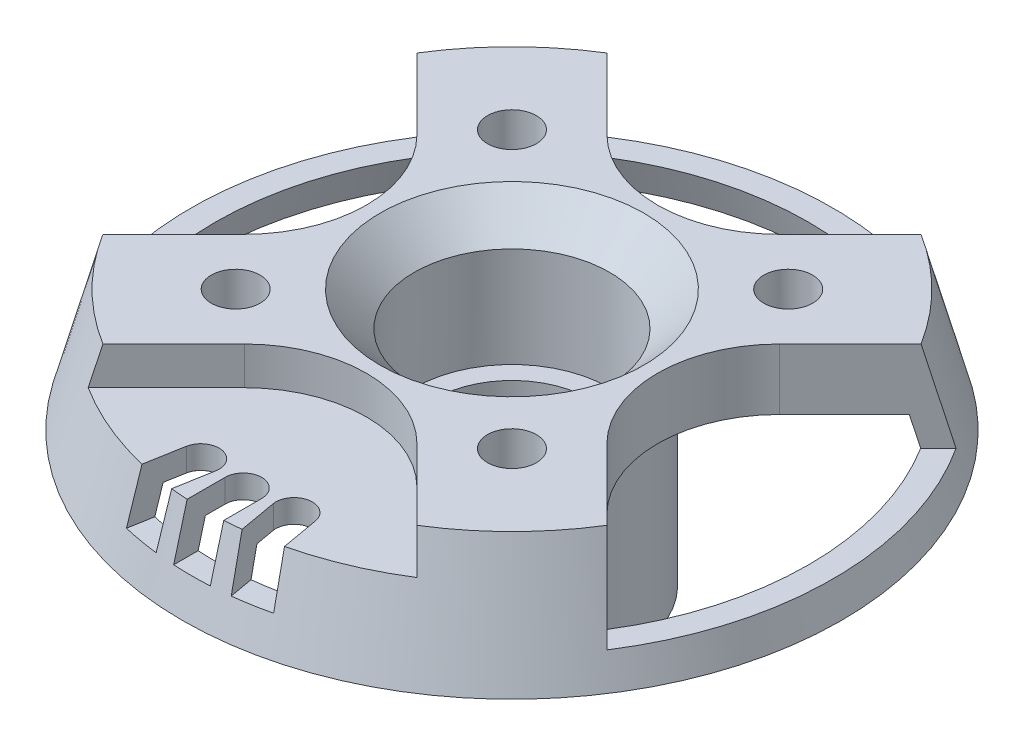
SolidWorks part; units mm, degrees
ref_plane "Front Plane" through (0, 0, 0) normal (0, 0, 1) x (1, 0, 0)
ref_plane "Top Plane" through (0, 0, 0) normal (0, 1, 0) x (1, 0, 0)
ref_plane "Right Plane" through (0, 0, 0) normal (1, 0, 0) x (0, 0, -1)
sketch "Sketch1" plane through (0, 0, 0) normal (0, 1, 0) x (1, 0, 0)
  circle A0 centre (0, 0) radius 13.5
  dimension "D1" = 27
extrude "Base size" add sketch "Sketch1" along normal blind 5
sketch "Sketch2" plane through (0, 5, 0) normal (0, 1, 0) x (1, 0, 0)
  line L0 (-9.5459, -9.5459) -> (9.5459, 9.5459) construction
  line L1 (-13.5, 0) -> (13.5, 0) construction
  line L2 (-9.5459, 9.5459) -> (9.5459, -9.5459) construction
  line L3 (0, 13.5) -> (0, -13.5) construction
  circle A0 centre (0, 0) radius 13.5 construction
  circle A1 centre (5.6569, 5.6569) radius 1
  circle A2 centre (-5.6569, -5.6569) radius 1
  circle A3 centre (5.6569, -5.6569) radius 1
  circle A4 centre (-5.6569, 5.6569) radius 1
  dimension "D2" = 2
  dimension "D1" = 45
  dimension "D3" = 16
extrude "Mounting holes" cut sketch "Sketch2" against normal up to next
sketch "Sketch3" plane through (0, 0, 0) normal (0, -1, 0) x (1, 0, 0)
  circle A0 centre (0, 0) radius 12.5
  circle A1 centre (0, 0) radius 13.5 construction
  dimension "D1" = 1
extrude "Rotor pocket" cut sketch "Sketch3" against normal blind 2.5 draft 15
chamfer "Outside chamfer" distance 5 angle 15 1 edges at (0, 5, 13.5) first distance on face at (0, 5, 13.5)
sketch "Sketch4" plane through (0, 5, 0) normal (0, 1, 0) x (1, 0, 0)
  line L0 (-8.5986, 8.5986) -> (8.5986, -8.5986) construction
  line L1 (-5.6569, 5.6569) -> (5.6569, 5.6569) construction
  line L2 (0, 12.1603) -> (0, -12.1603) construction
  line L3 (-12.1603, 0) -> (12.1603, 0) construction
  line L4 (-8.5986, -8.5986) -> (8.5986, 8.5986) construction
  line L5 (-10.5431, 6.6541) -> (6.6541, -10.5431)
  line L6 (-6.6541, -10.5431) -> (10.5431, 6.6541)
  line L7 (-6.6541, 10.5431) -> (10.5431, -6.6541)
  line L8 (-10.5431, -6.6541) -> (6.6541, 10.5431)
  line L9 (-10.5431, 6.6541) -> (-11.2903, 7.4012)
  line L10 (-6.6541, 10.5431) -> (-7.4012, 11.2903)
  line L11 (6.6541, 10.5431) -> (7.4012, 11.2903)
  line L12 (10.5431, 6.6541) -> (11.2903, 7.4012)
  line L13 (10.5431, -6.6541) -> (11.2903, -7.4012)
  line L14 (6.6541, -10.5431) -> (7.4012, -11.2903)
  line L15 (-6.6541, -10.5431) -> (-7.4012, -11.2903)
  line L16 (-10.5431, -6.6541) -> (-11.2903, -7.4012)
  circle A0 centre (0, 0) radius 12.1603 construction
  circle A1 centre (0, 0) radius 13.5
  circle A2 centre (0, 0) radius 13.5 construction
  circle M9 centre (0, 0) radius 12.1603
  dimension "D1" = 2.75
  dimension "D2" = 2.75
extrude "Bottom pockets top" cut sketch "Sketch4" against normal blind 1.55 contours L8 L5 M9 | L9 A1 L16 L8 L5 M9 | L7 L8 M9 | L11 A1 L10 L7 L8 M9 | L6 L7 M9 | L13 A1 L12 L6 L7 M9 | L15 A1 L14 L5 L6 M9 | L6 L5 M9 region at (-12.1626, 5, 0) region at (-8.9824, 5, 0) region at (0, 5, -8.9824) region at (0, 5, -12.1626) region at (0, 5, 8.9824) region at (0, 5, 12.1626) region at (8.9824, 5, 0) region at (12.1626, 5, 0)
sketch "Sketch5" plane through (0, 3.45, 0) normal (0, 1, 0) x (1, 0, 0)
  line L0 (-11.2903, 7.4012) -> (7.4012, -11.2903)
  line L1 (-10.3204, 6.4313) -> (-3.8891, 0) construction
  line L2 (7.4012, 11.2903) -> (-11.2903, -7.4012)
  line L3 (-10.3204, -6.4313) -> (-3.8891, 0) construction
  line L4 (-7.4012, 11.2903) -> (11.2903, -7.4012)
  line L5 (-6.4313, 10.3204) -> (0, 3.8891) construction
  line L6 (-7.4012, -11.2903) -> (11.2903, 7.4012)
  line L7 (3.8891, 0) -> (10.6216, 6.7325) construction
  circle A0 centre (0, 0) radius 13.5
  circle A1 centre (0, 0) radius 13.5 construction
  line M5 (-10.6216, -6.7325) -> (-3.8891, 0)
  line M6 (-3.8891, 0) -> (-10.6216, 6.7325)
  arc M7 (-10.6216, 6.7325) -> (-10.6216, -6.7325) centre (0, 0) ccw
extrude "Bottom pockets bottom" cut sketch "Sketch5" against normal offset from surface (2.15 mm away) 1.3 contours M7 M5 M6 | L0 A0 L2 M7 | L2 A0 L4 | L4 A0 L6 region at (-11.0626, 3.45, -6.9602) region at (-9.2333, 3.45, 0) region at (0, 3.45, -9.7912) region at (9.7912, 3.45, 0) up to face at (0, 0, -12.5)
fillet "Bottom pockets fillet" radius 5 4 edges at (0, 4.225, 3.8891) (3.8891, 3.75, 0) (0, 3.75, -3.8891) (-3.8891, 3.75, 0)
sketch "Sketch6" plane through (0, 5, 0) normal (0, 1, 0) x (1, 0, 0)
  circle A0 centre (0, 0) radius 4
  dimension "D1" = 8
extrude "Cut-Extrude5" cut sketch "Sketch6" against normal up to next
chamfer "Chamfer2" distance 1.4 angle 45 1 edges at (0, 5, 4)
sketch "Sketch7" plane through (0, 2.5, 0) normal (0, -1, 0) x (1, 0, 0)
  circle A0 centre (0, 0) radius 4
  circle A1 centre (0, 0) radius 4.8
  circle A2 centre (0, 0) radius 4 construction
  dimension "D1" = 0.8
extrude "Bearing bottom" add sketch "Sketch7" along normal blind 3
sketch "Sketch8" plane through (0, -0.5, 0) normal (0, -1, 0) x (1, 0, 0)
  circle A0 centre (0, 0) radius 4.8 construction
  circle A1 centre (0, 0) radius 4.8
  circle A2 centre (0, 0) radius 3.2
  circle A3 centre (0, 0) radius 4 construction
  dimension "D1" = 0.8
extrude "Bearing separator" add sketch "Sketch8" along normal blind 1
sketch "Sketch9" plane through (0, -1.5, 0) normal (0, -1, 0) x (1, 0, 0)
  circle A0 centre (0, 0) radius 4.8 construction
  circle A1 centre (0, 0) radius 4.8
  circle A2 centre (0, 0) radius 4 construction
  circle A3 centre (0, 0) radius 4
extrude "Bearing top" add sketch "Sketch9" along normal blind 4
sketch "Sketch10" plane through (0, 3.45, 0) normal (0, 1, 0) x (1, 0, 0)
  line L0 (0, -13.5) -> (0, 13.5) construction
  line L1 (0, 0) -> (0, -11) construction
  line L2 (0, 0) -> (-1.9101, -10.8329) construction
  line L3 (-2.6439, -10.6775) -> (-3.0788, -13.1442)
  line L4 (-1.1675, -10.9379) -> (-1.6025, -13.4046)
  line L5 (-0.75, -11) -> (-0.75, -13.4792)
  line L6 (2.6439, -10.6775) -> (3.0788, -13.1442)
  line L7 (1.1675, -10.9379) -> (1.6025, -13.4046)
  line L8 (0.75, -11) -> (0.75, -13.4792)
  circle A0 centre (0, 0) radius 11
  circle A1 centre (0, 0) radius 13.5 construction
  circle A2 centre (0, -11) radius 0.75
  circle A3 centre (-1.9101, -10.8329) radius 0.75
  circle A4 centre (1.9101, -10.8329) radius 0.75
  circle A5 centre (0, 0) radius 13.5
  arc M11 (-6.7325, -10.6216) -> (6.7325, -10.6216) centre (0, 0) ccw
  dimension "D1" = 2.5
  dimension "D2" = 1.5
  dimension "D4" = 10
  dimension "D3" = 2
extrude "Cut-Extrude6" cut sketch "Sketch10" against normal offset from surface (2.05 mm away) 1.4 contours A0 A3 | L3 A3 L4 A0 | A3 L3 L4 M11 | L3 A5 L4 M11 | L5 A5 L8 M11 | A2 L5 L8 M11 | A2 A0 | A0 A2 | A4 A0 | A4 L6 A0 L7 | L6 A4 L7 M11 | L7 A5 L6 M11 region at (-1.9646, 3.45, 11.1418) region at (-1.8541, 3.45, 10.5149) region at (-2.095, 3.45, 11.8813) region at (-2.2627, 3.45, 12.8326) region at (1.9646, 3.45, 11.1418) region at (1.8541, 3.45, 10.5149) region at (0, 3.45, 10.6771) region at (0, 3.45, 11.3137) region at (2.095, 3.45, 11.8813) region at (0, 3.45, 12.0643) region at (0, 3.45, 13.0306) region at (2.2627, 3.45, 12.8326) up to face at (0, 0, -12.5)
sketch "Sketch11" plane through (0, 5, 0) normal (0, 1, 0) x (1, 0, 0)
  line L0 (5.6569, -5.6569) -> (-5.6569, 5.6569) construction
  line L1 (5.6569, 5.6569) -> (-5.6569, -5.6569) construction
